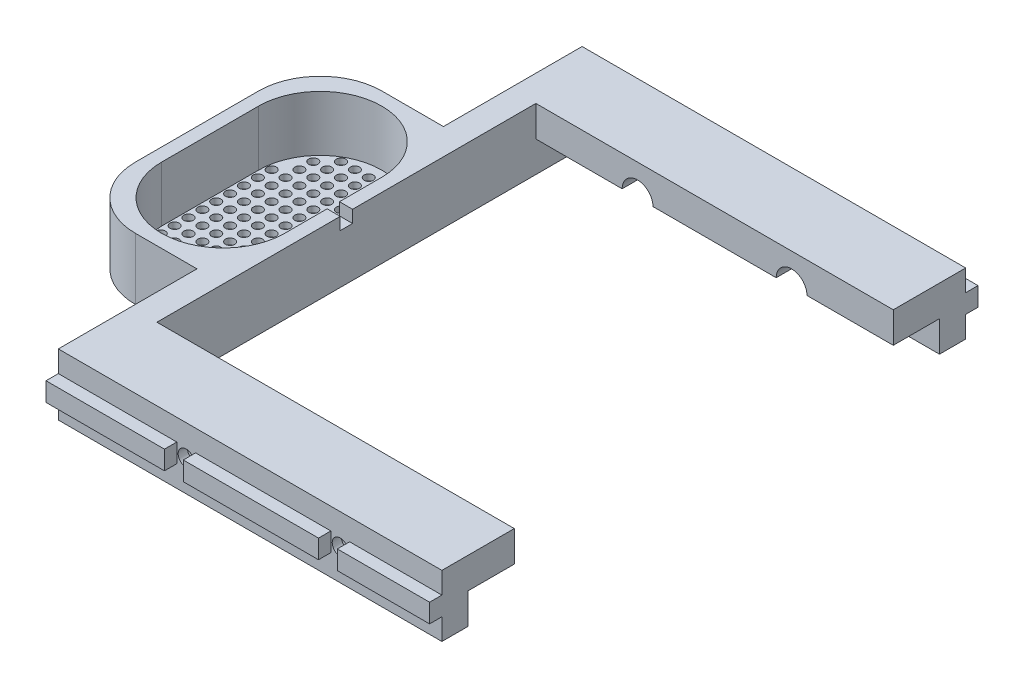
SolidWorks part; units mm, degrees
ref_plane "前视基准面" through (0, 0, 0) normal (0, 0, 1) x (1, 0, 0)
ref_plane "上视基准面" through (0, 0, 0) normal (0, 1, 0) x (1, 0, 0)
ref_plane "右视基准面" through (0, 0, 0) normal (1, 0, 0) x (0, 0, -1)
other "Configuration Table"
sketch "草图1" plane through (0, 0, 0) normal (0, 1, 0) x (1, 0, 0)
  line L5 (0, 85) -> (0, 76.5)
  line L6 (-116, 0) -> (-116, 76.5)
  line L7 (-116, 0) -> (-116, -76.5)
  line L8 (-116, 76.5) -> (0, 76.5)
  line L9 (-116, -76.5) -> (0, -76.5)
  line L10 (0, -76.5) -> (0, -85)
  line L15 (-124.5, 85) -> (0, 85)
  line L17 (-124.5, -85) -> (0, -85)
  line L18 (-144.5, 40) -> (-124.5, 40)
  line L19 (-144.5, -40) -> (-124.5, -40)
  line L20 (-124.5, -40) -> (-124.5, -85)
  line L21 (-164.5, 20) -> (-164.5, -20)
  line L22 (-124.5, 40) -> (-124.5, 85)
  arc A0 (-164.5, -20) -> (-144.5, -40) centre (-144.5, -20) ccw
  arc A2 (-164.5, 20) -> (-144.5, 40) centre (-144.5, 20) cw
extrude "凸台-拉伸1" add sketch "草图1" along normal blind 20 contours L19 L20 L17 L10 L9 L7 L6 L8 L5 L15 L22 L18 A2 L21 A0
sketch "草图4" plane through (0, 20, 0) normal (0, 1, 0) x (1, 0, 0)
  line L7 (-160.25, 15.75) -> (-160.25, -15.75)
  line L8 (-120.25, 15.75) -> (-120.25, -15.75)
  arc A0 (-160.25, 15.75) -> (-120.25, 15.75) centre (-140.25, 15.75) cw
  arc A1 (-160.25, -15.75) -> (-120.25, -15.75) centre (-140.25, -15.75) ccw
extrude "切除-拉伸2" cut sketch "草图4" against normal blind 18 contours L7 A1 L8 A0
sketch "草图5" plane through (0, 2, 0) normal (0, 1, 0) x (1, 0, 0)
  circle A3 centre (-140.25, 0) radius 1.5
  circle A4 centre (-135.75, 0) radius 1.5
  circle A5 centre (-131.25, 0) radius 1.5
  circle A6 centre (-126.75, 0) radius 1.5
  circle A7 centre (-122.25, 0) radius 1.5
  circle A8 centre (-144.75, 0) radius 1.5
  circle A9 centre (-149.25, 0) radius 1.5
  circle A10 centre (-153.75, 0) radius 1.5
  circle A11 centre (-158.25, 0) radius 1.5
  circle A12 centre (-122.25, 4.5) radius 1.5
  circle A13 centre (-126.75, 4.5) radius 1.5
  circle A14 centre (-131.25, 4.5) radius 1.5
  circle A15 centre (-135.75, 4.5) radius 1.5
  circle A16 centre (-140.25, 4.5) radius 1.5
  circle A17 centre (-144.75, 4.5) radius 1.5
  circle A18 centre (-149.25, 4.5) radius 1.5
  circle A19 centre (-153.75, 4.5) radius 1.5
  circle A20 centre (-158.25, 4.5) radius 1.5
  circle A21 centre (-122.25, 9) radius 1.5
  circle A22 centre (-126.75, 9) radius 1.5
  circle A23 centre (-131.25, 9) radius 1.5
  circle A24 centre (-135.75, 9) radius 1.5
  circle A25 centre (-140.25, 9) radius 1.5
  circle A26 centre (-144.75, 9) radius 1.5
  circle A27 centre (-149.25, 9) radius 1.5
  circle A28 centre (-153.75, 9) radius 1.5
  circle A29 centre (-158.25, 9) radius 1.5
  circle A30 centre (-122.25, 13.5) radius 1.5
  circle A31 centre (-126.75, 13.5) radius 1.5
  circle A32 centre (-131.25, 13.5) radius 1.5
  circle A33 centre (-135.75, 13.5) radius 1.5
  circle A34 centre (-140.25, 13.5) radius 1.5
  circle A35 centre (-144.75, 13.5) radius 1.5
  circle A36 centre (-149.25, 13.5) radius 1.5
  circle A37 centre (-153.75, 13.5) radius 1.5
  circle A38 centre (-158.25, 13.5) radius 1.5
  circle A39 centre (-122.25, 18) radius 1.5
  circle A40 centre (-126.75, 18) radius 1.5
  circle A41 centre (-131.25, 18) radius 1.5
  circle A42 centre (-135.75, 18) radius 1.5
  circle A43 centre (-140.25, 18) radius 1.5
  circle A44 centre (-144.75, 18) radius 1.5
  circle A45 centre (-149.25, 18) radius 1.5
  circle A46 centre (-153.75, 18) radius 1.5
  circle A47 centre (-158.25, 18) radius 1.5
  circle A48 centre (-158.25, -4.5) radius 1.5
  circle A49 centre (-153.75, -4.5) radius 1.5
  circle A50 centre (-149.25, -4.5) radius 1.5
  circle A51 centre (-144.75, -4.5) radius 1.5
  circle A52 centre (-140.25, -4.5) radius 1.5
  circle A53 centre (-135.75, -4.5) radius 1.5
  circle A54 centre (-131.25, -4.5) radius 1.5
  circle A55 centre (-126.75, -4.5) radius 1.5
  circle A56 centre (-122.25, -4.5) radius 1.5
  circle A57 centre (-158.25, -9) radius 1.5
  circle A58 centre (-153.75, -9) radius 1.5
  circle A59 centre (-149.25, -9) radius 1.5
  circle A60 centre (-144.75, -9) radius 1.5
  circle A61 centre (-140.25, -9) radius 1.5
  circle A62 centre (-135.75, -9) radius 1.5
  circle A63 centre (-131.25, -9) radius 1.5
  circle A64 centre (-126.75, -9) radius 1.5
  circle A65 centre (-122.25, -9) radius 1.5
  circle A66 centre (-158.25, -13.5) radius 1.5
  circle A67 centre (-153.75, -13.5) radius 1.5
  circle A68 centre (-149.25, -13.5) radius 1.5
  circle A69 centre (-144.75, -13.5) radius 1.5
  circle A70 centre (-140.25, -13.5) radius 1.5
  circle A71 centre (-135.75, -13.5) radius 1.5
  circle A72 centre (-131.25, -13.5) radius 1.5
  circle A73 centre (-126.75, -13.5) radius 1.5
  circle A74 centre (-122.25, -13.5) radius 1.5
  circle A75 centre (-158.25, -18) radius 1.5
  circle A76 centre (-153.75, -18) radius 1.5
  circle A77 centre (-149.25, -18) radius 1.5
  circle A78 centre (-144.75, -18) radius 1.5
  circle A79 centre (-140.25, -18) radius 1.5
  circle A80 centre (-135.75, -18) radius 1.5
  circle A81 centre (-131.25, -18) radius 1.5
  circle A82 centre (-126.75, -18) radius 1.5
  circle A83 centre (-122.25, -18) radius 1.5
  circle A84 centre (-153.75, 22.5) radius 1.5
  circle A85 centre (-149.25, 22.5) radius 1.5
  circle A86 centre (-144.75, 22.5) radius 1.5
  circle A87 centre (-140.25, 22.5) radius 1.5
  circle A88 centre (-135.75, 22.5) radius 1.5
  circle A89 centre (-131.25, 22.5) radius 1.5
  circle A90 centre (-126.75, 22.5) radius 1.5
  circle A91 centre (-153.75, 27) radius 1.5
  circle A92 centre (-149.25, 27) radius 1.5
  circle A93 centre (-144.75, 27) radius 1.5
  circle A94 centre (-140.25, 27) radius 1.5
  circle A95 centre (-135.75, 27) radius 1.5
  circle A96 centre (-131.25, 27) radius 1.5
  circle A97 centre (-126.75, 27) radius 1.5
  circle A98 centre (-131.25, 31.5) radius 1.5
  circle A99 centre (-135.75, 31.5) radius 1.5
  circle A100 centre (-140.25, 31.5) radius 1.5
  circle A101 centre (-144.75, 31.5) radius 1.5
  circle A102 centre (-149.25, 31.5) radius 1.5
  circle A103 centre (-126.75, -22.5) radius 1.5
  circle A104 centre (-131.25, -22.5) radius 1.5
  circle A105 centre (-135.75, -22.5) radius 1.5
  circle A106 centre (-140.25, -22.5) radius 1.5
  circle A107 centre (-144.75, -22.5) radius 1.5
  circle A108 centre (-149.25, -22.5) radius 1.5
  circle A109 centre (-153.75, -22.5) radius 1.5
  circle A110 centre (-126.75, -27) radius 1.5
  circle A111 centre (-131.25, -27) radius 1.5
  circle A112 centre (-135.75, -27) radius 1.5
  circle A113 centre (-140.25, -27) radius 1.5
  circle A114 centre (-144.75, -27) radius 1.5
  circle A115 centre (-149.25, -27) radius 1.5
  circle A116 centre (-153.75, -27) radius 1.5
  circle A117 centre (-131.25, -31.5) radius 1.5
  circle A118 centre (-135.75, -31.5) radius 1.5
  circle A119 centre (-140.25, -31.5) radius 1.5
  circle A120 centre (-144.75, -31.5) radius 1.5
  circle A121 centre (-149.25, -31.5) radius 1.5
  dimension "D1" = 5
  dimension "D2" = 5
  dimension "D3" = 5
  dimension "D4" = 5
  dimension "D5" = 3
  dimension "D6" = 2
  dimension "D7" = 3
  dimension "D8" = 2
extrude "切除-拉伸3" cut sketch "草图5" against normal blind 18
sketch "草图6" plane through (0, 0, -85) normal (0, 0, -1) x (-1, 0, 0)
  line L0 (0, 10) -> (0, 13.05)
  line L1 (0, 20) -> (0, 0) construction
  line L2 (124.5, 10) -> (124.5, 6.95)
  line L3 (124.5, 20) -> (124.5, 0) construction
  line L5 (124.5, 6.95) -> (0, 6.95)
  line L6 (124.5, 6.95) -> (124.5, 13.05)
  line L7 (124.5, 13.05) -> (0, 13.05)
  line L8 (0, 6.95) -> (0, 13.05)
extrude "凸台-拉伸2" add sketch "草图6" along normal blind 4 contours L6 L5 L8 L7
sketch "草图7" plane through (0, 0, 85) normal (0, 0, 1) x (1, 0, 0)
  line L0 (-124.5, 10) -> (-124.5, 13.05)
  line L1 (-124.5, 20) -> (-124.5, 0) construction
  line L2 (0, 10) -> (0, 6.95)
  line L3 (0, 20) -> (0, 0) construction
  line L5 (0, 6.95) -> (-124.5, 6.95)
  line L6 (0, 6.95) -> (0, 13.05)
  line L7 (0, 13.05) -> (-124.5, 13.05)
  line L8 (-124.5, 6.95) -> (-124.5, 13.05)
  line M3 (0, 0) -> (0, 20)
  line M5 (-124.5, 20) -> (-124.5, 0)
extrude "凸台-拉伸3" add sketch "草图7" along normal blind 4 contours L7 L5 M3 M5 region at (-62.25, 10, 85)
sketch "草图8" plane through (0, 0, -76.5) normal (0, 0, 1) x (1, 0, 0)
  line L0 (-116, 0) -> (0, 0)
  line L1 (-58, 0) -> (-58, 20)
  line L2 (-116, 20) -> (0, 20) construction
  line L3 (-58, 10) -> (-33, 10)
  line L4 (-58, 10) -> (-83, 10)
  circle A0 centre (-83, 10) radius 2.6
  circle A1 centre (-33, 10) radius 2.6
extrude "切除-拉伸4" cut sketch "草图8" against normal blind 12.5 contours A0 | A1 region at (-33, 12.5265, -76.5) region at (-85.5265, 10, -76.5)
sketch "草图9" plane through (0, 0, -89) normal (0, 0, -1) x (-1, 0, 0)
  circle A0 centre (33, 10) radius 2.6
  circle A1 centre (83, 10) radius 2.6
  circle M2 centre (83, 10) radius 2.6
  circle M3 centre (33, 10) radius 2.6
extrude "切除-拉伸5" cut sketch "草图9" against normal blind 10000 contours M3 | M2 | A0 region at (-33, 10, -89) region at (-83, 10, -89)
sketch "草图10" plane through (0, 0, 89) normal (0, 0, 1) x (1, 0, 0)
  line L0 (-83, 10) -> (-83, 13.05)
  line L1 (0, 13.05) -> (-124.5, 13.05) construction
  line L2 (-83, 13.05) -> (-86.05, 13.05)
  line L3 (-83, 10) -> (-83, 6.95)
  line L4 (0, 6.95) -> (-124.5, 6.95) construction
  line L5 (-83, 6.95) -> (-79.95, 6.95)
  line L6 (-33, 10) -> (-33, 13.05)
  line L7 (-86.05, 13.05) -> (-79.95, 13.05)
  line L8 (-86.05, 13.05) -> (-86.05, 6.95)
  line L9 (-86.05, 6.95) -> (-79.95, 6.95)
  line L10 (-79.95, 13.05) -> (-79.95, 6.95)
  line L11 (-33, 13.05) -> (-36.05, 13.05)
  line L12 (0, 13.05) -> (-124.5, 13.05) construction
  line L13 (-33, 10) -> (-33, 6.95)
  line L14 (-33, 6.95) -> (-29.95, 6.95)
  line L16 (-36.05, 13.05) -> (-29.95, 13.05)
  line L17 (-36.05, 13.05) -> (-36.05, 6.95)
  line L18 (-36.05, 6.95) -> (-29.95, 6.95)
  line L19 (-29.95, 13.05) -> (-29.95, 6.95)
  circle M5 centre (-33, 10) radius 2.6
  circle M6 centre (-83, 10) radius 2.6
  line M8 (0, 13.05) -> (-124.5, 13.05)
  line M10 (-124.5, 6.95) -> (0, 6.95)
extrude "切除-拉伸6" cut sketch "草图10" against normal blind 4 contours L10 L0 L3 M8 M6 M10 | L8 L3 L0 M8 M10 M6 | L17 L13 L6 M8 M10 M5 | L19 L6 L13 M8 M5 M10 region at (-85.6682, 10, 89) region at (-82.9318, 12.825, 89) region at (-34.525, 12.9818, 89) region at (-31.475, 12.9818, 89)
sketch "草图11" plane through (0, 0, -89) normal (0, 0, -1) x (-1, 0, 0)
  line L0 (33, 10) -> (33, 13.05)
  line L1 (124.5, 13.05) -> (0, 13.05) construction
  line L2 (33, 13.05) -> (29.95, 13.05)
  line L3 (83, 10) -> (83, 13.05)
  line L4 (29.95, 13.05) -> (36.05, 13.05)
  line L5 (33, 10) -> (33, 6.95)
  line L6 (124.5, 6.95) -> (0, 6.95) construction
  line L7 (33, 6.95) -> (36.05, 6.95)
  line L8 (29.95, 13.05) -> (29.95, 6.95)
  line L9 (29.95, 6.95) -> (36.05, 6.95)
  line L10 (36.05, 13.05) -> (36.05, 6.95)
  line L11 (83, 13.05) -> (79.95, 13.05)
  line L12 (83, 10) -> (83, 6.95)
  line L13 (83, 6.95) -> (86.05, 6.95)
  line L14 (124.5, 6.95) -> (0, 6.95) construction
  line L16 (79.95, 13.05) -> (86.05, 13.05)
  line L17 (79.95, 13.05) -> (79.95, 6.95)
  line L18 (79.95, 6.95) -> (86.05, 6.95)
  line L19 (86.05, 13.05) -> (86.05, 6.95)
  circle M5 centre (83, 10) radius 2.6
  circle M6 centre (33, 10) radius 2.6
  line M7 (124.5, 13.05) -> (0, 13.05)
  line M9 (0, 6.95) -> (124.5, 6.95)
extrude "切除-拉伸7" cut sketch "草图11" against normal blind 4 contours L17 L12 L3 M7 M9 M5 | L19 L3 L12 M7 M5 M9 | L8 L5 L0 M7 M9 M6 | L10 L0 L5 M7 M6 M9 region at (-30.3318, 10, -89) region at (-33.0682, 12.825, -89) region at (-81.475, 12.9818, -89) region at (-84.525, 12.9818, -89)
sketch "草图12" plane through (0, 0, 76.5) normal (0, 0, -1) x (-1, 0, 0)
  circle A0 centre (33, 10) radius 5
  circle A1 centre (83, 10) radius 5
extrude "切除-拉伸8" cut sketch "草图12" against normal blind 5.5
sketch "草图14" plane through (0, 0, -76.5) normal (0, 0, 1) x (1, 0, 0)
  circle A0 centre (-83, 10) radius 5
  circle A1 centre (-33, 10) radius 5
extrude "切除-拉伸9" cut sketch "草图14" against normal blind 5.5
sketch "草图15" plane through (0, 20, 0) normal (0, 1, 0) x (1, 0, 0)
  line L0 (-116, 76.5) -> (-116, 61.5)
  line L1 (-116, 76.5) -> (-116, -76.5) construction
  line L2 (-116, -76.5) -> (-116, -61.5)
  line L3 (-116, 61.5) -> (0, 61.5)
  line L4 (-116, 61.5) -> (-116, 76.5)
  line L5 (-116, 76.5) -> (0, 76.5)
  line L6 (0, 61.5) -> (0, 76.5)
  line L7 (-116, -76.5) -> (0, -76.5) construction
  line L8 (-116, -61.5) -> (0, -61.5)
  line L9 (-116, -61.5) -> (-116, -76.5)
  line L10 (-116, -76.5) -> (0, -76.5)
  line L11 (0, -61.5) -> (0, -76.5)
  line L12 (0, -76.5) -> (0, -85) construction
  line M16 (0, -76.5) -> (-116, -76.5)
  line M17 (-116, -76.5) -> (-116, 76.5)
  line M18 (-116, 76.5) -> (0, 76.5)
extrude "凸台-拉伸4" add sketch "草图15" against normal blind 10 contours L3 L6 M18 M17 | L11 L8 M17 M16 region at (-58, 20, -69) region at (-58, 20, 69)
sketch "草图16" plane through (0, 20, 0) normal (0, 1, 0) x (1, 0, 0)
  line L0 (-120.25, 15.75) -> (-120.25, -15.75) construction
  line L1 (-120.25, 0) -> (-116, 0)
  line L2 (-120.25, 0) -> (-120.25, 2)
  line L3 (-120.25, 2) -> (-116, 2)
  line L4 (-116, 0) -> (-116, 2)
  line L5 (-116, 61.5) -> (-116, -61.5) construction
  line L7 (-120.25, 0) -> (-116, 0)
  line L8 (-120.25, 0) -> (-120.25, -2)
  line L9 (-120.25, -2) -> (-116, -2)
  line L10 (-116, 0) -> (-116, -2)
  line M11 (-116, -61.5) -> (-116, 61.5)
  line M25 (-120.25, 15.75) -> (-120.25, -15.75)
extrude "切除-拉伸10" cut sketch "草图16" against normal blind 4 contours L3 L1 M25 M11 | L9 L1 M25 M11 region at (-118.125, 20, -1) region at (-118.125, 20, 1)
sketch "草图17" plane through (0, 0, -76.5) normal (0, 0, 1) x (1, 0, 0)
  line L0 (-88, 10) -> (-78, 10) construction
  line L1 (-38, 10) -> (-28, 10) construction
  circle A0 centre (-83, 10) radius 5
  circle A1 centre (-33, 10) radius 5
extrude "切除-拉伸11" cut sketch "草图17" along normal blind 155
